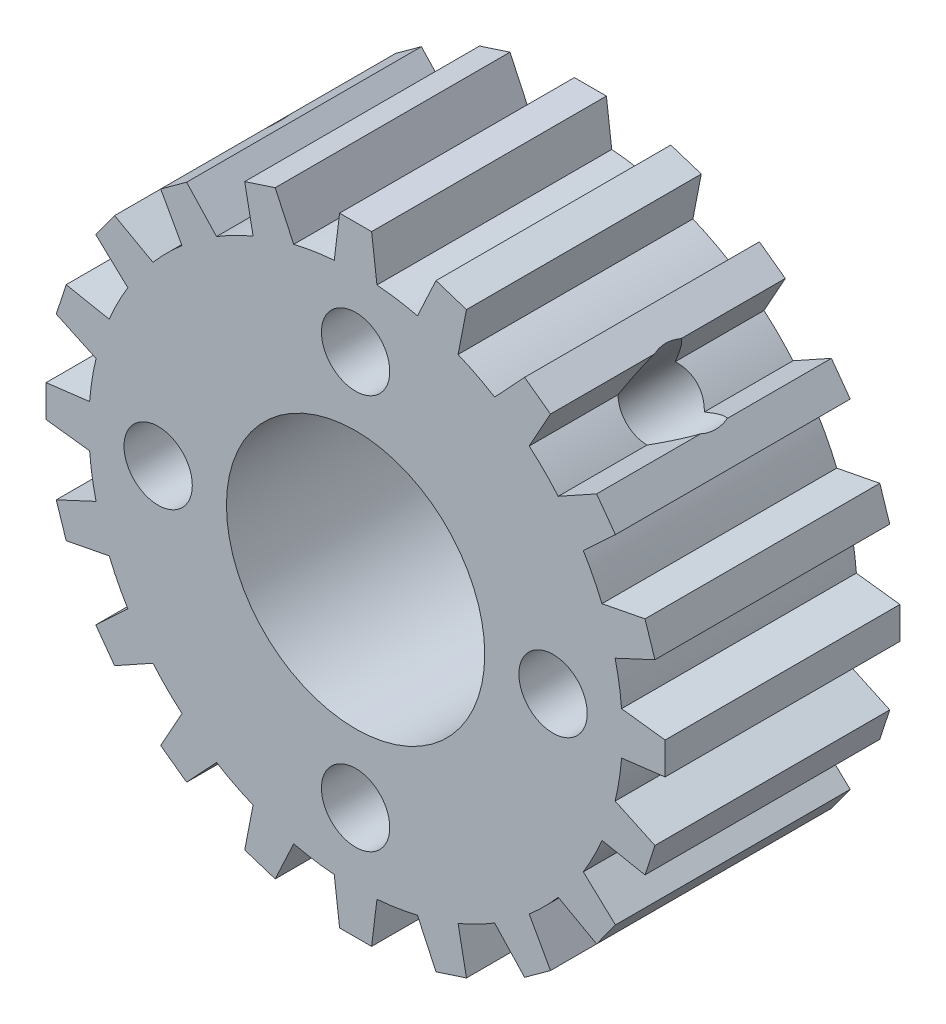
SolidWorks part; units mm, degrees
note: '?' marks a value the reader was unsure of.
ref_plane "正面" through (0, 0, 0) normal (0, 0, 1) x (1, 0, 0)
ref_plane "平面" through (0, 0, 0) normal (0, 1, 0) x (1, 0, 0)
ref_plane "右側面" through (0, 0, 0) normal (1, 0, 0) x (0, 0, -1)
sketch "ｽｹｯﾁ1" plane through (0, 0, 0) normal (0, 0, 1) x (1, 0, 0)
  line L0 (-0.75, 14.5) -> (-1, 12.4599)
  line L1 (-0.75, 14.5) -> (0.75, 14.5)
  line L2 (-0.75, 14.5) -> (-0.75, 10.5)
  line L3 (-0.75, 10.5) -> (0.75, 10.5)
  line L4 (0.75, 14.5) -> (0.75, 10.5)
  line L5 (-0.75, 14.5) -> (0.75, 10.5) construction
  line L6 (-0.75, 10.5) -> (0.75, 14.5) construction
  line L7 (0.75, 14.5) -> (1, 12.4599)
  line L8 (1, 12.4599) -> (-1, 12.4599)
  line L9 (3.7675, 14.0221) -> (5.194, 13.5586)
  line L10 (5.194, 13.5586) -> (4.8014, 11.5411)
  line L11 (3.7675, 14.0221) -> (2.8993, 12.1591)
  line L12 (7.9161, 12.1716) -> (9.1296, 11.2899)
  line L13 (9.1296, 11.2899) -> (8.1328, 9.4925)
  line L14 (7.9161, 12.1716) -> (6.5147, 10.6681)
  line L15 (11.2899, 9.1296) -> (12.1716, 7.9161)
  line L16 (12.1716, 7.9161) -> (10.6681, 6.5147)
  line L17 (11.2899, 9.1296) -> (9.4925, 8.1328)
  line L18 (13.5586, 5.194) -> (14.0221, 3.7675)
  line L19 (14.0221, 3.7675) -> (12.1591, 2.8993)
  line L20 (13.5586, 5.194) -> (11.5411, 4.8014)
  line L21 (14.5, 0.75) -> (14.5, -0.75)
  line L22 (14.5, -0.75) -> (12.4599, -1)
  line L23 (14.5, 0.75) -> (12.4599, 1)
  line L24 (14.0221, -3.7675) -> (13.5586, -5.194)
  line L25 (13.5586, -5.194) -> (11.5411, -4.8014)
  line L26 (14.0221, -3.7675) -> (12.1591, -2.8993)
  line L27 (12.1716, -7.9161) -> (11.2899, -9.1296)
  line L28 (11.2899, -9.1296) -> (9.4925, -8.1328)
  line L29 (12.1716, -7.9161) -> (10.6681, -6.5147)
  line L30 (9.1296, -11.2899) -> (7.9161, -12.1716)
  line L31 (7.9161, -12.1716) -> (6.5147, -10.6681)
  line L32 (9.1296, -11.2899) -> (8.1328, -9.4925)
  line L33 (5.194, -13.5586) -> (3.7675, -14.0221)
  line L34 (3.7675, -14.0221) -> (2.8993, -12.1591)
  line L35 (5.194, -13.5586) -> (4.8014, -11.5411)
  line L36 (0.75, -14.5) -> (-0.75, -14.5)
  line L37 (-0.75, -14.5) -> (-1, -12.4599)
  line L38 (0.75, -14.5) -> (1, -12.4599)
  line L39 (-3.7675, -14.0221) -> (-5.194, -13.5586)
  line L40 (-5.194, -13.5586) -> (-4.8014, -11.5411)
  line L41 (-3.7675, -14.0221) -> (-2.8993, -12.1591)
  line L42 (-7.9161, -12.1716) -> (-9.1296, -11.2899)
  line L43 (-9.1296, -11.2899) -> (-8.1328, -9.4925)
  line L44 (-7.9161, -12.1716) -> (-6.5147, -10.6681)
  line L45 (-11.2899, -9.1296) -> (-12.1716, -7.9161)
  line L46 (-12.1716, -7.9161) -> (-10.6681, -6.5147)
  line L47 (-11.2899, -9.1296) -> (-9.4925, -8.1328)
  line L48 (-13.5586, -5.194) -> (-14.0221, -3.7675)
  line L49 (-14.0221, -3.7675) -> (-12.1591, -2.8993)
  line L50 (-13.5586, -5.194) -> (-11.5411, -4.8014)
  line L51 (-14.5, -0.75) -> (-14.5, 0.75)
  line L52 (-14.5, 0.75) -> (-12.4599, 1)
  line L53 (-14.5, -0.75) -> (-12.4599, -1)
  line L54 (-14.0221, 3.7675) -> (-13.5586, 5.194)
  line L55 (-13.5586, 5.194) -> (-11.5411, 4.8014)
  line L56 (-9.25, 0) -> (0, -9.25) construction
  line L57 (0, -9.25) -> (9.25, 0) construction
  line L58 (9.25, 0) -> (0, 9.25) construction
  line L59 (0, 9.25) -> (-9.25, 0) construction
  line L60 (-14.0221, 3.7675) -> (-12.1591, 2.8993)
  line L61 (-12.1716, 7.9161) -> (-11.2899, 9.1296)
  line L62 (-11.2899, 9.1296) -> (-9.4925, 8.1328)
  line L63 (-12.1716, 7.9161) -> (-10.6681, 6.5147)
  line L64 (-9.1296, 11.2899) -> (-7.9161, 12.1716)
  line L65 (-7.9161, 12.1716) -> (-6.5147, 10.6681)
  line L66 (-9.1296, 11.2899) -> (-8.1328, 9.4925)
  line L67 (-5.194, 13.5586) -> (-3.7675, 14.0221)
  line L68 (-3.7675, 14.0221) -> (-2.8993, 12.1591)
  line L69 (-5.194, 13.5586) -> (-4.8014, 11.5411)
  line L70 (0, 0) -> (1, 12.4599) construction
  circle A0 centre (0, 0) radius 12.5
  circle A1 centre (0, 0) radius 6.05
  circle A2 centre (0, 0) radius 6.5407 construction
  circle A3 centre (-9.25, 0) radius 1.6
  circle A4 centre (0, 9.25) radius 1.6
  circle A5 centre (9.25, 0) radius 1.6
  circle A6 centre (0, -9.25) radius 1.6
  point P3 (0, 12.5)
  dimension "D1" = 25
  dimension "D8" = 12.1
  dimension "D10" = 3.2
  dimension "D11" = 3.2
  dimension "D12" = 3.2
  dimension "D13" = 3.2
  dimension "D2" = 1.5
  dimension "D3" = 2
  dimension "D4" = 0
  dimension "D5" = 2
  dimension "D7" = 12.5
  dimension "D9" = 18.5
  dimension "D6" = 20
extrude "ﾎﾞｽ - 押し出し1" add sketch "ｽｹｯﾁ1" along normal blind 11
ref_axis "軸1" through (0, 0, 11) along (0, 0, -1)?
ref_plane "平面1" through (0, 0, 0) normal (0.7071, -0.7071, 0) x (0, 0, -1)
sketch "ｽｹｯﾁ2" plane through (0, 0, 0) normal (0.7071, -0.7071, 0) x (0, 0, -1)
  circle A0 centre (-5.5, 0) radius 1.65
  dimension "D1" = 5.5
  dimension "D2" = 3.3
extrude "ｶｯﾄ - 押し出し3" cut sketch "ｽｹｯﾁ2" against normal through all
ref_plane "平面2" through (0, 0, 0) normal (-0.7071, -0.7071, 0) x (0, 0, -1)
sketch "ｽｹｯﾁ3" plane through (0, 0, 0) normal (-0.7071, -0.7071, 0) x (0, 0, -1)
  line L0 (-11, 6.05) -> (-11, -6.05) construction
  circle A0 centre (-5.5, 0) radius 1.65
  dimension "D1" = 5.5
  dimension "D2" = 3.3
extrude "ｶｯﾄ - 押し出し4" cut sketch "ｽｹｯﾁ3" against normal through all
